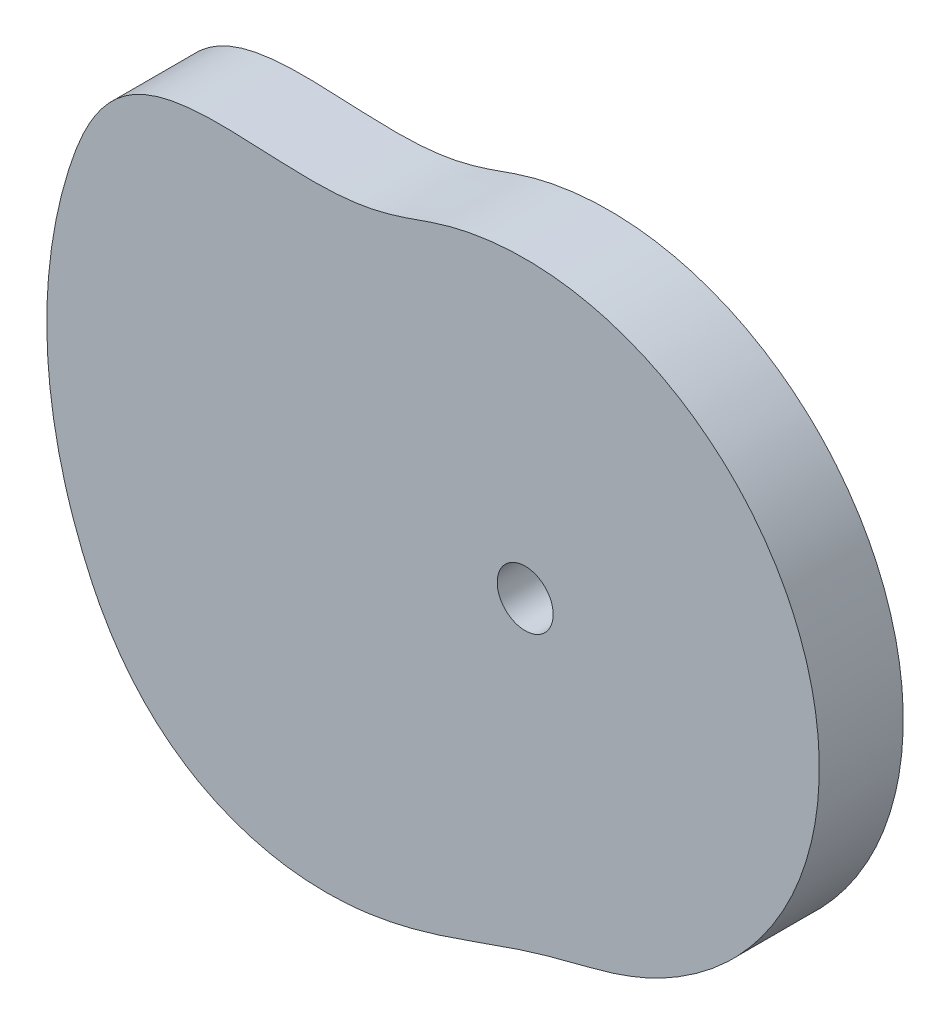
SolidWorks part; units mm, degrees
ref_plane "前视基准面" through (0, 0, 0) normal (0, 0, 1) x (1, 0, 0)
ref_plane "上视基准面" through (0, 0, 0) normal (0, 1, 0) x (1, 0, 0)
ref_plane "右视基准面" through (0, 0, 0) normal (1, 0, 0) x (0, 0, -1)
other "Configuration Table"
curve "曲线1"
sketch "草图1" plane through (0, 0, 0) normal (0, 0, 1) x (1, 0, 0)
  spline S0 degree 3 poles (71.0418, 77.4658) (70.3558, 78.0761) (69.666, 78.6826) (68.9824, 79.2894) (68.2921, 79.893) (67.5889, 80.4787) (66.8917, 81.0727) (66.1815, 81.6527) (65.4592, 82.219) (64.743, 82.7905) (64.018, 83.3518) (63.2913, 83.9128) (62.5525, 84.4601) (61.8092, 84.9989) (61.0716, 85.5435) (60.3217, 86.069) (59.5714, 86.5936) (58.8094, 87.0991) (58.0481, 87.6121) (57.2851, 88.1212) (56.508, 88.6121) (55.7293, 89.0988) (54.9554, 89.5922) (54.1673, 90.0611) (53.3826, 90.531) (52.5876, 90.9916) (51.7924, 91.4509) (50.9918, 91.8999) (50.1906, 92.3439) (49.379, 92.7682) (48.5708, 93.2047) (47.7488, 93.6177) (46.9352, 94.0438) (46.1089, 94.4378) (45.2904, 94.8444) (44.4569, 95.2305) (43.6268, 95.6209) (42.7874, 95.9918) (41.9493, 96.3584) (41.1122, 96.7362) (40.2591, 97.0779) (39.4121, 97.4317) (38.5618, 97.7714) (37.7068, 98.1003) (36.854, 98.4341) (35.9896, 98.7388) (35.127, 99.0509) (34.2637, 99.3642) (33.3894, 99.6483) (32.5216, 99.9416) (31.6489, 100.2237) (30.7694, 100.4879) (29.8934, 100.7648) (29.0097, 101.009) (28.1296, 101.2587) (27.2503, 101.5168) (26.3592, 101.7369) (25.473, 101.9754) (24.5796, 102.1786) (23.6868, 102.3905) (22.7956, 102.6036) (21.8965, 102.7894) (21.0012, 102.9823) (20.1008, 103.1609) (19.1979, 103.3335) (18.2929, 103.4876) (17.391, 103.6523) (16.4876, 103.8023) (15.5807, 103.9413) (14.6708, 104.0724) (13.7598, 104.1888) (12.8507, 104.3123) (11.9405, 104.4215) (11.0305, 104.5214) (10.1172, 104.613) (9.2032, 104.6882) (8.2905, 104.7725) (7.377, 104.8416) (6.4637, 104.9023) (5.5466, 104.9482) (4.6306, 105.006) (3.7132, 105.0277) (2.7968, 105.0626) (1.8801, 105.0824) (0.9633, 105.0878) (0.0467, 105.1062) (-0.87, 105.0875) (-1.7901, 105.0837) (-2.7066, 105.0576) (-3.6238, 105.0463) (-4.5398, 104.9965) (-5.4574, 104.9677) (-6.3728, 104.8937) (-7.2875, 104.8566) (-8.2004, 104.7812) (-9.1132, 104.6985) (-10.0272, 104.6229) (-10.9405, 104.5314) (-11.8505, 104.4315) (-12.7607, 104.3223) (-13.6698, 104.1988) (-14.5808, 104.0824) (-15.4906, 103.951) (-16.3978, 103.8135) (-17.3029, 103.6575) (-18.2078, 103.5135) (-19.1108, 103.3512) (-20.0109, 103.1814) (-20.9111, 103.0022) (-21.8065, 102.8095) (-22.7056, 102.6236) (-23.5968, 102.4105) (-24.4897, 102.1987) (-25.3829, 101.9952) (-26.2694, 101.7577) (-27.1586, 101.5341) (-28.044, 101.2889) (-28.9287, 101.0437) (-29.8068, 100.7806) (-30.6843, 100.5199) (-31.5587, 100.2531) (-32.4344, 99.9698) (-33.3168, 99.677) (-34.2166, 99.3829) (-35.1248, 99.0546) (-36.0548, 98.7408) (-36.9971, 98.4078) (-37.9526, 98.068) (-38.9301, 97.7269) (-39.9227, 97.3781) (-40.933, 97.029) (-41.9582, 96.6747) (-43.003, 96.329) (-44.0658, 95.9773) (-45.1441, 95.6254) (-46.2446, 95.2864) (-47.3643, 94.9549) (-48.5036, 94.6412) (-49.6527, 94.3117) (-50.827, 94.0213) (-52.0087, 93.7108) (-53.217, 93.4512) (-54.4338, 93.1732) (-55.6682, 92.9274) (-56.9187, 92.6963) (-58.1816, 92.4759) (-59.4617, 92.2755) (-60.7527, 92.0989) (-62.0519, 91.9255) (-63.3655, 91.776) (-64.6924, 91.6458) (-66.0297, 91.5387) (-67.3763, 91.4389) (-68.7324, 91.3425) (-70.1032, 91.2897) (-71.4798, 91.2378) (-72.8665, 91.1989) (-74.2598, 91.1654) (-75.6633, 91.1592) (-77.0734, 91.1578) (-78.4934, 91.1697) (-79.9203, 91.1836) (-81.3531, 91.236) (-82.7937, 91.2531) (-84.2399, 91.3124) (-85.6902, 91.3576) (-87.1469, 91.4177) (-88.6063, 91.4938) (-90.0736, 91.5466) (-91.5366, 91.6206) (-93.0033, 91.6902) (-94.4733, 91.7596) (-95.9431, 91.8322) (-97.4133, 91.8898) (-98.88, 91.9494) (-100.3464, 92.0127) (-101.81, 92.0589) (-103.2665, 92.1113) (-104.7164, 92.155) (-106.16, 92.1683) (-107.5966, 92.1918) (-109.0233, 92.2043) (-110.4401, 92.1911) (-111.8434, 92.1715) (-113.237, 92.1438) (-114.6172, 92.0941) (-115.9836, 92.0211) (-117.3341, 91.9447) (-118.6642, 91.844) (-119.9777, 91.7236) (-121.2746, 91.5845) (-122.5548, 91.4243) (-123.8119, 91.2457) (-125.0484, 91.0434) (-126.2625, 90.8263) (-127.4556, 90.584) (-128.6275, 90.3277) (-129.7763, 90.0344) (-130.9037, 89.7263) (-132.0088, 89.3974) (-133.0873, 89.0348) (-134.1478, 88.6553) (-135.1856, 88.2573) (-136.2028, 87.8343) (-137.201, 87.3864) (-138.1774, 86.9077) (-139.1314, 86.4021) (-140.0727, 85.8863) (-140.993, 85.3355) (-141.8907, 84.7544) (-142.7756, 84.1527) (-143.6454, 83.5217) (-144.5011, 82.8673) (-145.3394, 82.1779) (-146.1621, 81.4668) (-146.9698, 80.7169) (-147.7632, 79.9432) (-148.5493, 79.1387) (-149.3172, 78.3023) (-150.0628, 77.4285) (-150.811, 76.5408) (-151.5262, 75.6071) (-152.2369, 74.6474) (-152.9378, 73.6599) (-153.6169, 72.6366) (-154.2859, 71.5858) (-154.9501, 70.5118) (-155.5742, 69.3923) (-156.206, 68.2602) (-156.8177, 67.0973) (-157.4066, 65.9048) (-157.9835, 64.6865) (-158.5593, 63.4471) (-159.1004, 62.1783) (-159.6491, 60.8965) (-160.1635, 59.586) (-160.6737, 58.256) (-161.1775, 56.9084) (-161.6488, 55.5362) (-162.1375, 54.1581) (-162.5935, 52.7555) (-163.0408, 51.3413) (-163.4833, 49.9187) (-163.9098, 48.491) (-164.3366, 47.0604) (-164.7263, 45.619) (-165.1377, 44.1847) (-165.4989, 42.7363) (-165.8716, 41.2913) (-166.2339, 39.8425) (-166.5698, 38.3907) (-166.9056, 36.9394) (-167.2103, 35.4808) (-167.5131, 34.018) (-167.8002, 32.554) (-168.0821, 31.0877) (-168.354, 29.6219) (-168.6009, 28.1507) (-168.8421, 26.6775) (-169.0731, 25.2048) (-169.282, 23.7274) (-169.4809, 22.2506) (-169.6744, 20.7713) (-169.8407, 19.2904) (-170.0027, 17.8073) (-170.1501, 16.3237) (-170.2951, 14.8377) (-170.411, 13.3503) (-170.5211, 11.8603) (-170.6245, 10.3707) (-170.7008, 8.8802) (-170.7721, 7.3902) (-170.8308, 5.9002) (-170.8848, 4.4103) (-170.9099, 2.9201) (-170.9357, 1.4301) (-170.9275, -0.06) (-170.9345, -1.5534) (-170.9146, -3.0469) (-170.8675, -4.5399) (-170.8357, -6.0304) (-170.7699, -7.5201) (-170.7048, -9.0106) (-170.6107, -10.5003) (-170.5126, -11.9871) (-170.4003, -13.4736) (-170.2844, -14.961) (-170.1416, -16.4472) (-169.991, -17.9304) (-169.8344, -19.4113) (-169.6508, -20.8905) (-169.462, -22.3707) (-169.2607, -23.8505) (-169.0552, -25.3284) (-168.8209, -26.8007) (-168.581, -28.2707) (-168.3342, -29.7419) (-168.0606, -31.2107) (-167.783, -32.6779) (-167.4906, -34.1408) (-167.1939, -35.6022) (-166.8722, -37.0579) (-166.5407, -38.5109) (-166.204, -39.9626) (-165.8404, -41.4109) (-165.4733, -42.8584) (-165.0902, -44.3009) (-164.7044, -45.7431) (-164.2894, -47.1765) (-163.8832, -48.6129) (-163.4553, -50.0404) (-162.9976, -51.4592) (-162.5541, -52.8835) (-162.0824, -54.2986) (-161.6, -55.7111) (-161.1161, -57.1212) (-160.5973, -58.519) (-160.0942, -59.924) (-159.561, -61.3183) (-159.0261, -62.7117) (-158.4571, -64.0888) (-157.906, -65.4719) (-157.3199, -66.8414) (-156.7334, -68.2048) (-156.1417, -69.5637) (-155.5345, -70.9118) (-154.9024, -72.2445) (-154.2727, -73.5745) (-153.6211, -74.8889) (-152.9674, -76.2006) (-152.2784, -77.4909) (-151.595, -78.783) (-150.8808, -80.059) (-150.1674, -81.3315) (-149.4179, -82.5808) (-148.6771, -83.8318) (-147.8988, -85.0635) (-147.1165, -86.2919) (-146.3013, -87.4998) (-145.4825, -88.703) (-144.6433, -89.8963) (-143.7713, -91.0701) (-142.8946, -92.2393) (-142.0025, -93.3966) (-141.0808, -94.5327) (-140.1454, -95.6636) (-139.1772, -96.7734) (-138.208, -97.8832) (-137.2003, -98.9633) (-136.1808, -100.0339) (-135.1439, -101.0939) (-134.0801, -102.1337) (-133.0028, -103.1634) (-131.9029, -104.1778) (-130.7694, -105.1598) (-129.6328, -106.1486) (-128.4622, -107.1003) (-127.2813, -108.0478) (-126.0716, -108.9645) (-124.8386, -109.864) (-123.5955, -110.7526) (-122.3298, -111.618) (-121.0377, -112.4535) (-119.7351, -113.2836) (-118.4086, -114.088) (-117.0614, -114.8617) (-115.7027, -115.6272) (-114.3191, -116.3544) (-112.9197, -117.0662) (-111.5005, -117.7513) (-110.074, -118.4304) (-108.6178, -119.0493) (-107.1609, -119.6782) (-105.6823, -120.2645) (-104.1904, -120.8235) (-102.6874, -121.3647) (-101.1764, -121.886) (-99.6468, -122.3649) (-98.1094, -122.8226) (-96.5626, -123.2687) (-94.999, -123.6631) (-93.4319, -124.0413) (-91.8616, -124.4096) (-90.2813, -124.7202) (-88.6967, -125.0289) (-87.1043, -125.2893) (-85.51, -125.5499) (-83.911, -125.7516) (-82.3111, -125.9431) (-80.7115, -126.1151) (-79.1079, -126.256) (-77.5039, -126.3618) (-75.9008, -126.4553) (-74.3037, -126.5165) (-72.7067, -126.5382) (-71.1133, -126.5709) (-69.5233, -126.5383) (-67.9396, -126.5164) (-66.3625, -126.4561) (-64.7931, -126.3605) (-63.2293, -126.2634) (-61.6719, -126.1461) (-60.1222, -125.9941) (-58.583, -125.8202) (-57.051, -125.6481) (-55.5328, -125.43) (-54.0248, -125.2157) (-52.5283, -124.9734) (-51.0426, -124.711) (-49.5641, -124.4468) (-48.0995, -124.1492) (-46.6436, -123.8575) (-45.2067, -123.5297) (-43.7774, -123.2146) (-42.3653, -122.8722) (-40.9601, -122.526) (-39.5736, -122.1489) (-38.1941, -121.7861) (-36.8337, -121.3988) (-35.4795, -121.0266) (-34.1436, -120.6192) (-32.8111, -120.2241) (-31.4961, -119.8117) (-30.1911, -119.4038) (-28.9031, -118.9807) (-27.6227, -118.5618) (-26.3531, -118.1408) (-25.091, -117.7235) (-23.8457, -117.2928) (-22.6098, -116.8604) (-21.3849, -116.4289) (-20.1607, -116.0142) (-18.9528, -115.5814) (-17.7547, -115.1496) (-16.5626, -114.7322) (-15.3798, -114.3104) (-14.205, -113.8886) (-13.0301, -113.4857) (-11.8769, -113.0567) (-10.7197, -112.6609) (-9.5725, -112.2623) (-8.4321, -111.8573) (-7.2923, -111.4729) (-6.1645, -111.0801) (-5.0418, -110.6979) (-3.9223, -110.3331) (-2.812, -109.9573) (-1.6996, -109.6011) (-0.5944, -109.2399) (0.5055, -108.8896) (1.6006, -108.5518) (2.6834, -108.2059) (3.7725, -107.8948) (4.8434, -107.5558) (5.9206, -107.252) (6.9853, -106.9387) (8.0503, -106.6412) (9.1054, -106.3389) (10.1603, -106.0509) (11.2056, -105.7595) (12.2457, -105.4797) (13.2801, -105.2102) (14.307, -104.9413) (15.33, -104.6702) (16.3426, -104.4006) (17.3532, -104.1394) (18.3524, -103.8796) (19.3518, -103.6336) (20.3351, -103.3672) (21.3189, -103.1252) (22.2853, -102.8583) (23.2499, -102.6097) (24.2088, -102.3646) (25.155, -102.0973) (26.0989, -101.8548) (27.0266, -101.5896) (27.9519, -101.3333) (28.8619, -101.0586) (29.7738, -100.806) (30.6647, -100.5168) (31.5563, -100.2563) (32.4341, -99.969) (33.3041, -99.6823) (34.1766, -99.3928) (35.0346, -99.0775) (35.9039, -98.7843) (36.7616, -98.4608) (37.6195, -98.1287) (38.4798, -97.8047) (39.3289, -97.4573) (40.1823, -97.1269) (41.0214, -96.7554) (41.8697, -96.4038) (42.7098, -96.0335) (43.5417, -95.6464) (44.3798, -95.2736) (45.2099, -94.8834) (46.0291, -94.4781) (46.8551, -94.0835) (47.6694, -93.6587) (48.4875, -93.2417) (49.3049, -92.8225) (50.1071, -92.3809) (50.9127, -91.9416) (51.7092, -91.4886) (52.5107, -91.0438) (53.3018, -90.5798) (54.0925, -90.1108) (54.8774, -89.6313) (55.6613, -89.154) (56.4287, -88.658) (57.2061, -88.1728) (57.9643, -87.6597) (58.7359, -87.1621) (59.4876, -86.6413) (60.2426, -86.1203) (60.9925, -85.5901) (61.7379, -85.0517) (62.4817, -84.5135) (63.2092, -83.9589) (63.9426, -83.4101) (64.6713, -82.8526) (65.3922, -82.2794) (66.1087, -81.7025) (66.8186, -81.1224) (67.5226, -80.5398) (68.2222, -79.9492) (68.9217, -79.3524) (69.6091, -78.7427) (70.2885, -78.1284) (70.9765, -77.524) (71.6346, -76.8875) (72.3166, -76.2738) (72.9683, -75.6283) (73.6299, -74.9933) (74.2819, -74.3486) (74.9324, -73.7023) (75.5687, -73.042) (76.2032, -72.3797) (76.8285, -71.7086) (77.4629, -71.0454) (78.0719, -70.3583) (78.6797, -69.6698) (79.2893, -68.9823) (79.8931, -68.2921) (80.4787, -67.5889) (81.0727, -66.8917) (81.6527, -66.1815) (82.219, -65.4592) (82.7905, -64.743) (83.3518, -64.018) (83.9128, -63.2913) (84.4601, -62.5525) (84.9989, -61.8092) (85.5435, -61.0716) (86.069, -60.3217) (86.5936, -59.5714) (87.0991, -58.8094) (87.6121, -58.0481) (88.1212, -57.2851) (88.6121, -56.508) (89.0988, -55.7293) (89.5922, -54.9554) (90.0611, -54.1673) (90.531, -53.3826) (90.9916, -52.5876) (91.4509, -51.7924) (91.8999, -50.9918) (92.3439, -50.1906) (92.7682, -49.379) (93.2047, -48.5708) (93.6177, -47.7488) (94.0438, -46.9352) (94.4378, -46.1089) (94.8444, -45.2904) (95.2305, -44.4569) (95.6209, -43.6268) (95.9918, -42.7874) (96.3584, -41.9493) (96.7362, -41.1122) (97.0779, -40.2591) (97.4317, -39.4121) (97.7714, -38.5618) (98.1004, -37.7068) (98.4337, -36.8539) (98.7413, -35.9871) (99.0465, -35.1221) (99.3667, -34.2613) (99.6479, -33.3893) (99.9417, -32.5217) (100.2237, -31.6488) (100.4879, -30.7694) (100.7649, -29.8934) (101.0087, -29.0096) (101.2607, -28.1269) (101.5132, -27.246) (101.7389, -26.3564) (101.9751, -25.4729) (102.1787, -24.5797) (102.3905, -23.6868) (102.6036, -22.7956) (102.7894, -21.8965) (102.9823, -21.0012) (103.1609, -20.1008) (103.3335, -19.1979) (103.4876, -18.2929) (103.6523, -17.391) (103.8023, -16.4876) (103.9413, -15.5807) (104.0724, -14.6708) (104.1888, -13.7598) (104.3123, -12.8507) (104.4215, -11.9405) (104.5214, -11.0305) (104.613, -10.1172) (104.6882, -9.2032) (104.7725, -8.2905) (104.8416, -7.377) (104.9023, -6.4637) (104.9482, -5.5466) (105.006, -4.6306) (105.0277, -3.7132) (105.0626, -2.7968) (105.0824, -1.8801) (105.0878, -0.9633) (105.1062, -0.0467) (105.0875, 0.87) (105.0837, 1.7901) (105.0576, 2.7066) (105.0463, 3.6238) (104.9965, 4.5398) (104.9677, 5.4574) (104.8937, 6.3728) (104.8566, 7.2875) (104.7812, 8.2004) (104.6985, 9.1132) (104.6229, 10.0272) (104.5314, 10.9405) (104.4315, 11.8505) (104.3223, 12.7607) (104.1988, 13.6698) (104.0824, 14.5808) (103.951, 15.4906) (103.8135, 16.3978) (103.6575, 17.3029) (103.5135, 18.2078) (103.3512, 19.1108) (103.1814, 20.0109) (103.0022, 20.9111) (102.8095, 21.8065) (102.6236, 22.7056) (102.4105, 23.5968) (102.1987, 24.4897) (101.9952, 25.3829) (101.7577, 26.2694) (101.5341, 27.1586) (101.2889, 28.044) (101.0437, 28.9287) (100.7806, 29.8068) (100.5199, 30.6843) (100.2532, 31.5587) (99.9696, 32.4343) (99.6821, 33.304) (99.3929, 34.1767) (99.0775, 35.0346) (98.7843, 35.9039) (98.4608, 36.7616) (98.1287, 37.6195) (97.8047, 38.4798) (97.4573, 39.3289) (97.1269, 40.1823) (96.7554, 41.0214) (96.4038, 41.8697) (96.0335, 42.7098) (95.6464, 43.5417) (95.2736, 44.3798) (94.8834, 45.2099) (94.4781, 46.0291) (94.0835, 46.8551) (93.6587, 47.6694) (93.2417, 48.4875) (92.8225, 49.3049) (92.3809, 50.1071) (91.9416, 50.9127) (91.4886, 51.7092) (91.0438, 52.5107) (90.5798, 53.3018) (90.1108, 54.0925) (89.6313, 54.8774) (89.154, 55.6613) (88.658, 56.4287) (88.1728, 57.2061) (87.6597, 57.9643) (87.1621, 58.7359) (86.6413, 59.4876) (86.1203, 60.2426) (85.5901, 60.9925) (85.0517, 61.7379) (84.5135, 62.4817) (83.9589, 63.2092) (83.4101, 63.9426) (82.8526, 64.6713) (82.2794, 65.3922) (81.7025, 66.1087) (81.1224, 66.8186) (80.5398, 67.5226) (79.9492, 68.2222) (79.3524, 68.9217) (78.7427, 69.6091) (78.1284, 70.2885) (77.524, 70.9765) (76.8875, 71.6346) (76.2738, 72.3166) (75.6283, 72.9683) (74.9933, 73.6299) (74.3486, 74.2819) (73.7023, 74.9324) (73.042, 75.5687) (72.3797, 76.2032) (71.7087, 76.8286) (71.0418, 77.4658) (70.3558, 78.0761) (69.666, 78.6826) knots -0.003364 -0.002246 -0.001128 0 0.001103 0.002222 0.003334 0.004447 0.00556 0.006675 0.007792 0.008908 0.010017 0.011136 0.012257 0.013371 0.014485 0.015601 0.016711 0.017824 0.018937 0.02006 0.02117 0.02229 0.02341 0.024517 0.025634 0.026746 0.027868 0.028984 0.030094 0.031209 0.032324 0.033444 0.034565 0.035674 0.036783 0.037898 0.039024 0.040129 0.041245 0.042361 0.043479 0.044597 0.04571 0.046819 0.047939 0.04905 0.050162 0.051285 0.0524 0.053515 0.054626 0.055745 0.056864 0.057977 0.059089 0.060201 0.061319 0.062437 0.063549 0.06466 0.065784 0.066891 0.068009 0.069125 0.070239 0.071362 0.072474 0.073583 0.074702 0.07582 0.076936 0.078052 0.079167 0.08028 0.081392 0.082515 0.083625 0.084735 0.085856 0.086964 0.088084 0.089204 0.090311 0.09143 0.092548 0.093655 0.094773 0.095892 0.097011 0.098118 0.099237 0.100357 0.101466 0.102586 0.103696 0.104807 0.10593 0.107041 0.108154 0.109269 0.110385 0.111501 0.112619 0.113738 0.114848 0.115969 0.11708 0.118194 0.11931 0.120429 0.121535 0.122659 0.123771 0.124882 0.126 0.127118 0.128227 0.129351 0.130467 0.131571 0.13269 0.133801 0.134928 0.136081 0.137254 0.13845 0.139661 0.1409 0.142149 0.143438 0.144737 0.146048 0.147394 0.148751 0.150132 0.151532 0.152951 0.154391 0.155842 0.157311 0.158803 0.160299 0.161818 0.163356 0.16489 0.166457 0.168032 0.169616 0.17121 0.172813 0.174438 0.176073 0.177706 0.179364 0.181031 0.18271 0.184389 0.186091 0.187794 0.189508 0.191235 0.192973 0.194713 0.196464 0.198228 0.199992 0.201757 0.203546 0.205323 0.207112 0.20889 0.210679 0.21248 0.214257 0.216046 0.217835 0.219611 0.221387 0.223151 0.224902 0.226653 0.228392 0.230106 0.231821 0.233511 0.23519 0.236858 0.238503 0.240124 0.241724 0.243314 0.244882 0.24643 0.247945 0.249452 0.250928 0.252385 0.253828 0.255252 0.256649 0.258033 0.259402 0.260757 0.262087 0.26342 0.264747 0.266052 0.267358 0.268662 0.269963 0.271259 0.272565 0.273883 0.275187 0.276523 0.277848 0.279207 0.280565 0.281951 0.283348 0.284755 0.286185 0.287637 0.289111 0.290602 0.292116 0.293655 0.295207 0.29679 0.298384 0.299999 0.301641 0.303301 0.304984 0.306673 0.308387 0.310118 0.311869 0.313634 0.31541 0.317202 0.319013 0.320821 0.322637 0.324449 0.326266 0.328083 0.329891 0.33171 0.333527 0.335338 0.337146 0.338961 0.340773 0.342595 0.344402 0.34622 0.348033 0.349844 0.351665 0.35347 0.355286 0.3571 0.358912 0.360722 0.362543 0.36435 0.366168 0.367984 0.3698 0.371614 0.373428 0.375241 0.377054 0.378866 0.380678 0.382489 0.384301 0.386125 0.387937 0.38975 0.391563 0.393376 0.395191 0.397007 0.398812 0.400629 0.402449 0.404258 0.406068 0.40788 0.409695 0.411511 0.413328 0.415137 0.416948 0.418761 0.420578 0.422398 0.424208 0.42602 0.427837 0.429646 0.431456 0.433273 0.435093 0.436903 0.438717 0.440538 0.442347 0.444162 0.445973 0.447785 0.449603 0.451414 0.453229 0.455041 0.456853 0.458673 0.460486 0.462297 0.464107 0.465916 0.46773 0.469521 0.471323 0.473123 0.474901 0.47669 0.478474 0.480247 0.482026 0.483806 0.485581 0.487347 0.489119 0.490884 0.492661 0.494432 0.496199 0.49797 0.499752 0.501532 0.503301 0.505082 0.506869 0.508653 0.510454 0.512243 0.514041 0.515846 0.517652 0.519466 0.521282 0.523109 0.524937 0.526777 0.528611 0.530459 0.532313 0.534178 0.536033 0.537905 0.539791 0.541667 0.543563 0.545457 0.547356 0.549264 0.551184 0.553104 0.555026 0.556955 0.558892 0.560827 0.562766 0.564719 0.566657 0.568611 0.570571 0.572529 0.574493 0.576451 0.578411 0.580367 0.58234 0.584297 0.586259 0.588218 0.590174 0.592127 0.594089 0.596038 0.597985 0.599918 0.601864 0.603797 0.605719 0.607641 0.609553 0.611454 0.613356 0.61525 0.617133 0.619007 0.620872 0.622728 0.624563 0.626402 0.628231 0.630041 0.631853 0.633647 0.635417 0.637192 0.638947 0.640696 0.642433 0.64415 0.645855 0.647555 0.649244 0.650925 0.652582 0.654231 0.655869 0.657496 0.659111 0.660718 0.662302 0.663887 0.665455 0.667017 0.668567 0.670101 0.671624 0.673147 0.674654 0.676154 0.677635 0.679115 0.680584 0.682049 0.683503 0.684941 0.686375 0.687798 0.689216 0.690635 0.692039 0.693427 0.694815 0.696185 0.697558 0.698913 0.700267 0.701607 0.702946 0.70427 0.705595 0.706905 0.708199 0.709494 0.710777 0.71206 0.713316 0.714584 0.715826 0.71707 0.7183 0.719521 0.720727 0.721933 0.723131 0.724314 0.725488 0.72665 0.727816 0.728955 0.730101 0.731232 0.732343 0.73347 0.734573 0.735696 0.736804 0.737919 0.739039 0.740159 0.741272 0.742386 0.743497 0.744619 0.745735 0.746845 0.747966 0.749081 0.75019 0.7513 0.75242 0.75354 0.75465 0.75577 0.756881 0.757997 0.759113 0.760224 0.761342 0.762466 0.763579 0.764689 0.765799 0.766922 0.768028 0.769148 0.770257 0.771374 0.772498 0.773611 0.774723 0.775834 0.776953 0.778069 0.779193 0.780308 0.781413 0.782527 0.783648 0.784767 0.785878 0.786989 0.788107 0.789217 0.790335 0.791453 0.792562 0.793679 0.794797 0.795907 0.797025 0.798143 0.799254 0.800374 0.801493 0.802605 0.803718 0.804831 0.805946 0.807063 0.808179 0.809288 0.810407 0.811528 0.812642 0.813756 0.814872 0.815982 0.817095 0.818208 0.819331 0.820441 0.821561 0.822681 0.823788 0.824905 0.826017 0.827139 0.828255 0.829365 0.83048 0.831595 0.832716 0.833836 0.834945 0.836054 0.837169 0.838295 0.8394 0.840516 0.841632 0.84275 0.843868 0.844981 0.84609 0.84721 0.848321 0.849444 0.850556 0.851671 0.852786 0.853897 0.855016 0.856135 0.857248 0.85836 0.859484 0.86059 0.861708 0.86282 0.863931 0.865055 0.866162 0.86728 0.868396 0.86951 0.870633 0.871745 0.872854 0.873973 0.875091 0.876207 0.877323 0.878438 0.879551 0.880663 0.881786 0.882896 0.884006 0.885127 0.886235 0.887355 0.888475 0.889582 0.8907 0.891819 0.892926 0.894044 0.895163 0.896282 0.897389 0.898508 0.899628 0.900737 0.901857 0.902967 0.904078 0.9052 0.906312 0.907425 0.90854 0.909656 0.910772 0.91189 0.913009 0.914119 0.91524 0.916351 0.917465 0.918581 0.919699 0.920806 0.92193 0.923042 0.924153 0.925271 0.926389 0.927498 0.928622 0.929738 0.930842 0.931961 0.933072 0.934199 0.935302 0.936425 0.937533 0.938648 0.939768 0.940888 0.942001 0.943115 0.944226 0.945348 0.946464 0.947574 0.948695 0.94981 0.950919 0.952029 0.953149 0.954269 0.955379 0.956499 0.957609 0.958726 0.959842 0.960953 0.962071 0.963195 0.964308 0.965418 0.966528 0.967651 0.968757 0.969877 0.970986 0.972103 0.973227 0.97434 0.975452 0.976563 0.977682 0.978798 0.979922 0.981037 0.982142 0.983256 0.984377 0.985496 0.986607 0.987718 0.988836 0.989946 0.991064 0.992182 0.993291 0.994408 0.995526 0.996636 0.997754 0.998872 1 1.001103 1.002222 1.003334 only from (70.35, 78.08) to (70.35, 78.08) construction
  spline S1 degree 3 poles (71.0418, 77.4658) (70.3558, 78.0761) (69.666, 78.6826) (68.9824, 79.2894) (68.2921, 79.893) (67.5889, 80.4787) (66.8917, 81.0727) (66.1815, 81.6527) (65.4592, 82.219) (64.743, 82.7905) (64.018, 83.3518) (63.2913, 83.9128) (62.5525, 84.4601) (61.8092, 84.9989) (61.0716, 85.5435) (60.3217, 86.069) (59.5714, 86.5936) (58.8094, 87.0991) (58.0481, 87.6121) (57.2851, 88.1212) (56.508, 88.6121) (55.7293, 89.0988) (54.9554, 89.5922) (54.1673, 90.0611) (53.3826, 90.531) (52.5876, 90.9916) (51.7924, 91.4509) (50.9918, 91.8999) (50.1906, 92.3439) (49.379, 92.7682) (48.5708, 93.2047) (47.7488, 93.6177) (46.9352, 94.0438) (46.1089, 94.4378) (45.2904, 94.8444) (44.4569, 95.2305) (43.6268, 95.6209) (42.7874, 95.9918) (41.9493, 96.3584) (41.1122, 96.7362) (40.2591, 97.0779) (39.4121, 97.4317) (38.5618, 97.7714) (37.7068, 98.1003) (36.854, 98.4341) (35.9896, 98.7388) (35.127, 99.0509) (34.2637, 99.3642) (33.3894, 99.6483) (32.5216, 99.9416) (31.6489, 100.2237) (30.7694, 100.4879) (29.8934, 100.7648) (29.0097, 101.009) (28.1296, 101.2587) (27.2503, 101.5168) (26.3592, 101.7369) (25.473, 101.9754) (24.5796, 102.1786) (23.6868, 102.3905) (22.7956, 102.6036) (21.8965, 102.7894) (21.0012, 102.9823) (20.1008, 103.1609) (19.1979, 103.3335) (18.2929, 103.4876) (17.391, 103.6523) (16.4876, 103.8023) (15.5807, 103.9413) (14.6708, 104.0724) (13.7598, 104.1888) (12.8507, 104.3123) (11.9405, 104.4215) (11.0305, 104.5214) (10.1172, 104.613) (9.2032, 104.6882) (8.2905, 104.7725) (7.377, 104.8416) (6.4637, 104.9023) (5.5466, 104.9482) (4.6306, 105.006) (3.7132, 105.0277) (2.7968, 105.0626) (1.8801, 105.0824) (0.9633, 105.0878) (0.0467, 105.1062) (-0.87, 105.0875) (-1.7901, 105.0837) (-2.7066, 105.0576) (-3.6238, 105.0463) (-4.5398, 104.9965) (-5.4574, 104.9677) (-6.3728, 104.8937) (-7.2875, 104.8566) (-8.2004, 104.7812) (-9.1132, 104.6985) (-10.0272, 104.6229) (-10.9405, 104.5314) (-11.8505, 104.4315) (-12.7607, 104.3223) (-13.6698, 104.1988) (-14.5808, 104.0824) (-15.4906, 103.951) (-16.3978, 103.8135) (-17.3029, 103.6575) (-18.2078, 103.5135) (-19.1108, 103.3512) (-20.0109, 103.1814) (-20.9111, 103.0022) (-21.8065, 102.8095) (-22.7056, 102.6236) (-23.5968, 102.4105) (-24.4897, 102.1987) (-25.3829, 101.9952) (-26.2694, 101.7577) (-27.1586, 101.5341) (-28.044, 101.2889) (-28.9287, 101.0437) (-29.8068, 100.7806) (-30.6843, 100.5199) (-31.5587, 100.2531) (-32.4344, 99.9698) (-33.3168, 99.677) (-34.2166, 99.3829) (-35.1248, 99.0546) (-36.0548, 98.7408) (-36.9971, 98.4078) (-37.9526, 98.068) (-38.9301, 97.7269) (-39.9227, 97.3781) (-40.933, 97.029) (-41.9582, 96.6747) (-43.003, 96.329) (-44.0658, 95.9773) (-45.1441, 95.6254) (-46.2446, 95.2864) (-47.3643, 94.9549) (-48.5036, 94.6412) (-49.6527, 94.3117) (-50.827, 94.0213) (-52.0087, 93.7108) (-53.217, 93.4512) (-54.4338, 93.1732) (-55.6682, 92.9274) (-56.9187, 92.6963) (-58.1816, 92.4759) (-59.4617, 92.2755) (-60.7527, 92.0989) (-62.0519, 91.9255) (-63.3655, 91.776) (-64.6924, 91.6458) (-66.0297, 91.5387) (-67.3763, 91.4389) (-68.7324, 91.3425) (-70.1032, 91.2897) (-71.4798, 91.2378) (-72.8665, 91.1989) (-74.2598, 91.1654) (-75.6633, 91.1592) (-77.0734, 91.1578) (-78.4934, 91.1697) (-79.9203, 91.1836) (-81.3531, 91.236) (-82.7937, 91.2531) (-84.2399, 91.3124) (-85.6902, 91.3576) (-87.1469, 91.4177) (-88.6063, 91.4938) (-90.0736, 91.5466) (-91.5366, 91.6206) (-93.0033, 91.6902) (-94.4733, 91.7596) (-95.9431, 91.8322) (-97.4133, 91.8898) (-98.88, 91.9494) (-100.3464, 92.0127) (-101.81, 92.0589) (-103.2665, 92.1113) (-104.7164, 92.155) (-106.16, 92.1683) (-107.5966, 92.1918) (-109.0233, 92.2043) (-110.4401, 92.1911) (-111.8434, 92.1715) (-113.237, 92.1438) (-114.6172, 92.0941) (-115.9836, 92.0211) (-117.3341, 91.9447) (-118.6642, 91.844) (-119.9777, 91.7236) (-121.2746, 91.5845) (-122.5548, 91.4243) (-123.8119, 91.2457) (-125.0484, 91.0434) (-126.2625, 90.8263) (-127.4556, 90.584) (-128.6275, 90.3277) (-129.7763, 90.0344) (-130.9037, 89.7263) (-132.0088, 89.3974) (-133.0873, 89.0348) (-134.1478, 88.6553) (-135.1856, 88.2573) (-136.2028, 87.8343) (-137.201, 87.3864) (-138.1774, 86.9077) (-139.1314, 86.4021) (-140.0727, 85.8863) (-140.993, 85.3355) (-141.8907, 84.7544) (-142.7756, 84.1527) (-143.6454, 83.5217) (-144.5011, 82.8673) (-145.3394, 82.1779) (-146.1621, 81.4668) (-146.9698, 80.7169) (-147.7632, 79.9432) (-148.5493, 79.1387) (-149.3172, 78.3023) (-150.0628, 77.4285) (-150.811, 76.5408) (-151.5262, 75.6071) (-152.2369, 74.6474) (-152.9378, 73.6599) (-153.6169, 72.6366) (-154.2859, 71.5858) (-154.9501, 70.5118) (-155.5742, 69.3923) (-156.206, 68.2602) (-156.8177, 67.0973) (-157.4066, 65.9048) (-157.9835, 64.6865) (-158.5593, 63.4471) (-159.1004, 62.1783) (-159.6491, 60.8965) (-160.1635, 59.586) (-160.6737, 58.256) (-161.1775, 56.9084) (-161.6488, 55.5362) (-162.1375, 54.1581) (-162.5935, 52.7555) (-163.0408, 51.3413) (-163.4833, 49.9187) (-163.9098, 48.491) (-164.3366, 47.0604) (-164.7263, 45.619) (-165.1377, 44.1847) (-165.4989, 42.7363) (-165.8716, 41.2913) (-166.2339, 39.8425) (-166.5698, 38.3907) (-166.9056, 36.9394) (-167.2103, 35.4808) (-167.5131, 34.018) (-167.8002, 32.554) (-168.0821, 31.0877) (-168.354, 29.6219) (-168.6009, 28.1507) (-168.8421, 26.6775) (-169.0731, 25.2048) (-169.282, 23.7274) (-169.4809, 22.2506) (-169.6744, 20.7713) (-169.8407, 19.2904) (-170.0027, 17.8073) (-170.1501, 16.3237) (-170.2951, 14.8377) (-170.411, 13.3503) (-170.5211, 11.8603) (-170.6245, 10.3707) (-170.7008, 8.8802) (-170.7721, 7.3902) (-170.8308, 5.9002) (-170.8848, 4.4103) (-170.9099, 2.9201) (-170.9357, 1.4301) (-170.9275, -0.06) (-170.9345, -1.5534) (-170.9146, -3.0469) (-170.8675, -4.5399) (-170.8357, -6.0304) (-170.7699, -7.5201) (-170.7048, -9.0106) (-170.6107, -10.5003) (-170.5126, -11.9871) (-170.4003, -13.4736) (-170.2844, -14.961) (-170.1416, -16.4472) (-169.991, -17.9304) (-169.8344, -19.4113) (-169.6508, -20.8905) (-169.462, -22.3707) (-169.2607, -23.8505) (-169.0552, -25.3284) (-168.8209, -26.8007) (-168.581, -28.2707) (-168.3342, -29.7419) (-168.0606, -31.2107) (-167.783, -32.6779) (-167.4906, -34.1408) (-167.1939, -35.6022) (-166.8722, -37.0579) (-166.5407, -38.5109) (-166.204, -39.9626) (-165.8404, -41.4109) (-165.4733, -42.8584) (-165.0902, -44.3009) (-164.7044, -45.7431) (-164.2894, -47.1765) (-163.8832, -48.6129) (-163.4553, -50.0404) (-162.9976, -51.4592) (-162.5541, -52.8835) (-162.0824, -54.2986) (-161.6, -55.7111) (-161.1161, -57.1212) (-160.5973, -58.519) (-160.0942, -59.924) (-159.561, -61.3183) (-159.0261, -62.7117) (-158.4571, -64.0888) (-157.906, -65.4719) (-157.3199, -66.8414) (-156.7334, -68.2048) (-156.1417, -69.5637) (-155.5345, -70.9118) (-154.9024, -72.2445) (-154.2727, -73.5745) (-153.6211, -74.8889) (-152.9674, -76.2006) (-152.2784, -77.4909) (-151.595, -78.783) (-150.8808, -80.059) (-150.1674, -81.3315) (-149.4179, -82.5808) (-148.6771, -83.8318) (-147.8988, -85.0635) (-147.1165, -86.2919) (-146.3013, -87.4998) (-145.4825, -88.703) (-144.6433, -89.8963) (-143.7713, -91.0701) (-142.8946, -92.2393) (-142.0025, -93.3966) (-141.0808, -94.5327) (-140.1454, -95.6636) (-139.1772, -96.7734) (-138.208, -97.8832) (-137.2003, -98.9633) (-136.1808, -100.0339) (-135.1439, -101.0939) (-134.0801, -102.1337) (-133.0028, -103.1634) (-131.9029, -104.1778) (-130.7694, -105.1598) (-129.6328, -106.1486) (-128.4622, -107.1003) (-127.2813, -108.0478) (-126.0716, -108.9645) (-124.8386, -109.864) (-123.5955, -110.7526) (-122.3298, -111.618) (-121.0377, -112.4535) (-119.7351, -113.2836) (-118.4086, -114.088) (-117.0614, -114.8617) (-115.7027, -115.6272) (-114.3191, -116.3544) (-112.9197, -117.0662) (-111.5005, -117.7513) (-110.074, -118.4304) (-108.6178, -119.0493) (-107.1609, -119.6782) (-105.6823, -120.2645) (-104.1904, -120.8235) (-102.6874, -121.3647) (-101.1764, -121.886) (-99.6468, -122.3649) (-98.1094, -122.8226) (-96.5626, -123.2687) (-94.999, -123.6631) (-93.4319, -124.0413) (-91.8616, -124.4096) (-90.2813, -124.7202) (-88.6967, -125.0289) (-87.1043, -125.2893) (-85.51, -125.5499) (-83.911, -125.7516) (-82.3111, -125.9431) (-80.7115, -126.1151) (-79.1079, -126.256) (-77.5039, -126.3618) (-75.9008, -126.4553) (-74.3037, -126.5165) (-72.7067, -126.5382) (-71.1133, -126.5709) (-69.5233, -126.5383) (-67.9396, -126.5164) (-66.3625, -126.4561) (-64.7931, -126.3605) (-63.2293, -126.2634) (-61.6719, -126.1461) (-60.1222, -125.9941) (-58.583, -125.8202) (-57.051, -125.6481) (-55.5328, -125.43) (-54.0248, -125.2157) (-52.5283, -124.9734) (-51.0426, -124.711) (-49.5641, -124.4468) (-48.0995, -124.1492) (-46.6436, -123.8575) (-45.2067, -123.5297) (-43.7774, -123.2146) (-42.3653, -122.8722) (-40.9601, -122.526) (-39.5736, -122.1489) (-38.1941, -121.7861) (-36.8337, -121.3988) (-35.4795, -121.0266) (-34.1436, -120.6192) (-32.8111, -120.2241) (-31.4961, -119.8117) (-30.1911, -119.4038) (-28.9031, -118.9807) (-27.6227, -118.5618) (-26.3531, -118.1408) (-25.091, -117.7235) (-23.8457, -117.2928) (-22.6098, -116.8604) (-21.3849, -116.4289) (-20.1607, -116.0142) (-18.9528, -115.5814) (-17.7547, -115.1496) (-16.5626, -114.7322) (-15.3798, -114.3104) (-14.205, -113.8886) (-13.0301, -113.4857) (-11.8769, -113.0567) (-10.7197, -112.6609) (-9.5725, -112.2623) (-8.4321, -111.8573) (-7.2923, -111.4729) (-6.1645, -111.0801) (-5.0418, -110.6979) (-3.9223, -110.3331) (-2.812, -109.9573) (-1.6996, -109.6011) (-0.5944, -109.2399) (0.5055, -108.8896) (1.6006, -108.5518) (2.6834, -108.2059) (3.7725, -107.8948) (4.8434, -107.5558) (5.9206, -107.252) (6.9853, -106.9387) (8.0503, -106.6412) (9.1054, -106.3389) (10.1603, -106.0509) (11.2056, -105.7595) (12.2457, -105.4797) (13.2801, -105.2102) (14.307, -104.9413) (15.33, -104.6702) (16.3426, -104.4006) (17.3532, -104.1394) (18.3524, -103.8796) (19.3518, -103.6336) (20.3351, -103.3672) (21.3189, -103.1252) (22.2853, -102.8583) (23.2499, -102.6097) (24.2088, -102.3646) (25.155, -102.0973) (26.0989, -101.8548) (27.0266, -101.5896) (27.9519, -101.3333) (28.8619, -101.0586) (29.7738, -100.806) (30.6647, -100.5168) (31.5563, -100.2563) (32.4341, -99.969) (33.3041, -99.6823) (34.1766, -99.3928) (35.0346, -99.0775) (35.9039, -98.7843) (36.7616, -98.4608) (37.6195, -98.1287) (38.4798, -97.8047) (39.3289, -97.4573) (40.1823, -97.1269) (41.0214, -96.7554) (41.8697, -96.4038) (42.7098, -96.0335) (43.5417, -95.6464) (44.3798, -95.2736) (45.2099, -94.8834) (46.0291, -94.4781) (46.8551, -94.0835) (47.6694, -93.6587) (48.4875, -93.2417) (49.3049, -92.8225) (50.1071, -92.3809) (50.9127, -91.9416) (51.7092, -91.4886) (52.5107, -91.0438) (53.3018, -90.5798) (54.0925, -90.1108) (54.8774, -89.6313) (55.6613, -89.154) (56.4287, -88.658) (57.2061, -88.1728) (57.9643, -87.6597) (58.7359, -87.1621) (59.4876, -86.6413) (60.2426, -86.1203) (60.9925, -85.5901) (61.7379, -85.0517) (62.4817, -84.5135) (63.2092, -83.9589) (63.9426, -83.4101) (64.6713, -82.8526) (65.3922, -82.2794) (66.1087, -81.7025) (66.8186, -81.1224) (67.5226, -80.5398) (68.2222, -79.9492) (68.9217, -79.3524) (69.6091, -78.7427) (70.2885, -78.1284) (70.9765, -77.524) (71.6346, -76.8875) (72.3166, -76.2738) (72.9683, -75.6283) (73.6299, -74.9933) (74.2819, -74.3486) (74.9324, -73.7023) (75.5687, -73.042) (76.2032, -72.3797) (76.8285, -71.7086) (77.4629, -71.0454) (78.0719, -70.3583) (78.6797, -69.6698) (79.2893, -68.9823) (79.8931, -68.2921) (80.4787, -67.5889) (81.0727, -66.8917) (81.6527, -66.1815) (82.219, -65.4592) (82.7905, -64.743) (83.3518, -64.018) (83.9128, -63.2913) (84.4601, -62.5525) (84.9989, -61.8092) (85.5435, -61.0716) (86.069, -60.3217) (86.5936, -59.5714) (87.0991, -58.8094) (87.6121, -58.0481) (88.1212, -57.2851) (88.6121, -56.508) (89.0988, -55.7293) (89.5922, -54.9554) (90.0611, -54.1673) (90.531, -53.3826) (90.9916, -52.5876) (91.4509, -51.7924) (91.8999, -50.9918) (92.3439, -50.1906) (92.7682, -49.379) (93.2047, -48.5708) (93.6177, -47.7488) (94.0438, -46.9352) (94.4378, -46.1089) (94.8444, -45.2904) (95.2305, -44.4569) (95.6209, -43.6268) (95.9918, -42.7874) (96.3584, -41.9493) (96.7362, -41.1122) (97.0779, -40.2591) (97.4317, -39.4121) (97.7714, -38.5618) (98.1004, -37.7068) (98.4337, -36.8539) (98.7413, -35.9871) (99.0465, -35.1221) (99.3667, -34.2613) (99.6479, -33.3893) (99.9417, -32.5217) (100.2237, -31.6488) (100.4879, -30.7694) (100.7649, -29.8934) (101.0087, -29.0096) (101.2607, -28.1269) (101.5132, -27.246) (101.7389, -26.3564) (101.9751, -25.4729) (102.1787, -24.5797) (102.3905, -23.6868) (102.6036, -22.7956) (102.7894, -21.8965) (102.9823, -21.0012) (103.1609, -20.1008) (103.3335, -19.1979) (103.4876, -18.2929) (103.6523, -17.391) (103.8023, -16.4876) (103.9413, -15.5807) (104.0724, -14.6708) (104.1888, -13.7598) (104.3123, -12.8507) (104.4215, -11.9405) (104.5214, -11.0305) (104.613, -10.1172) (104.6882, -9.2032) (104.7725, -8.2905) (104.8416, -7.377) (104.9023, -6.4637) (104.9482, -5.5466) (105.006, -4.6306) (105.0277, -3.7132) (105.0626, -2.7968) (105.0824, -1.8801) (105.0878, -0.9633) (105.1062, -0.0467) (105.0875, 0.87) (105.0837, 1.7901) (105.0576, 2.7066) (105.0463, 3.6238) (104.9965, 4.5398) (104.9677, 5.4574) (104.8937, 6.3728) (104.8566, 7.2875) (104.7812, 8.2004) (104.6985, 9.1132) (104.6229, 10.0272) (104.5314, 10.9405) (104.4315, 11.8505) (104.3223, 12.7607) (104.1988, 13.6698) (104.0824, 14.5808) (103.951, 15.4906) (103.8135, 16.3978) (103.6575, 17.3029) (103.5135, 18.2078) (103.3512, 19.1108) (103.1814, 20.0109) (103.0022, 20.9111) (102.8095, 21.8065) (102.6236, 22.7056) (102.4105, 23.5968) (102.1987, 24.4897) (101.9952, 25.3829) (101.7577, 26.2694) (101.5341, 27.1586) (101.2889, 28.044) (101.0437, 28.9287) (100.7806, 29.8068) (100.5199, 30.6843) (100.2532, 31.5587) (99.9696, 32.4343) (99.6821, 33.304) (99.3929, 34.1767) (99.0775, 35.0346) (98.7843, 35.9039) (98.4608, 36.7616) (98.1287, 37.6195) (97.8047, 38.4798) (97.4573, 39.3289) (97.1269, 40.1823) (96.7554, 41.0214) (96.4038, 41.8697) (96.0335, 42.7098) (95.6464, 43.5417) (95.2736, 44.3798) (94.8834, 45.2099) (94.4781, 46.0291) (94.0835, 46.8551) (93.6587, 47.6694) (93.2417, 48.4875) (92.8225, 49.3049) (92.3809, 50.1071) (91.9416, 50.9127) (91.4886, 51.7092) (91.0438, 52.5107) (90.5798, 53.3018) (90.1108, 54.0925) (89.6313, 54.8774) (89.154, 55.6613) (88.658, 56.4287) (88.1728, 57.2061) (87.6597, 57.9643) (87.1621, 58.7359) (86.6413, 59.4876) (86.1203, 60.2426) (85.5901, 60.9925) (85.0517, 61.7379) (84.5135, 62.4817) (83.9589, 63.2092) (83.4101, 63.9426) (82.8526, 64.6713) (82.2794, 65.3922) (81.7025, 66.1087) (81.1224, 66.8186) (80.5398, 67.5226) (79.9492, 68.2222) (79.3524, 68.9217) (78.7427, 69.6091) (78.1284, 70.2885) (77.524, 70.9765) (76.8875, 71.6346) (76.2738, 72.3166) (75.6283, 72.9683) (74.9933, 73.6299) (74.3486, 74.2819) (73.7023, 74.9324) (73.042, 75.5687) (72.3797, 76.2032) (71.7087, 76.8286) (71.0418, 77.4658) (70.3558, 78.0761) (69.666, 78.6826) knots -0.003364 -0.002246 -0.001128 0 0.001103 0.002222 0.003334 0.004447 0.00556 0.006675 0.007792 0.008908 0.010017 0.011136 0.012257 0.013371 0.014485 0.015601 0.016711 0.017824 0.018937 0.02006 0.02117 0.02229 0.02341 0.024517 0.025634 0.026746 0.027868 0.028984 0.030094 0.031209 0.032324 0.033444 0.034565 0.035674 0.036783 0.037898 0.039024 0.040129 0.041245 0.042361 0.043479 0.044597 0.04571 0.046819 0.047939 0.04905 0.050162 0.051285 0.0524 0.053515 0.054626 0.055745 0.056864 0.057977 0.059089 0.060201 0.061319 0.062437 0.063549 0.06466 0.065784 0.066891 0.068009 0.069125 0.070239 0.071362 0.072474 0.073583 0.074702 0.07582 0.076936 0.078052 0.079167 0.08028 0.081392 0.082515 0.083625 0.084735 0.085856 0.086964 0.088084 0.089204 0.090311 0.09143 0.092548 0.093655 0.094773 0.095892 0.097011 0.098118 0.099237 0.100357 0.101466 0.102586 0.103696 0.104807 0.10593 0.107041 0.108154 0.109269 0.110385 0.111501 0.112619 0.113738 0.114848 0.115969 0.11708 0.118194 0.11931 0.120429 0.121535 0.122659 0.123771 0.124882 0.126 0.127118 0.128227 0.129351 0.130467 0.131571 0.13269 0.133801 0.134928 0.136081 0.137254 0.13845 0.139661 0.1409 0.142149 0.143438 0.144737 0.146048 0.147394 0.148751 0.150132 0.151532 0.152951 0.154391 0.155842 0.157311 0.158803 0.160299 0.161818 0.163356 0.16489 0.166457 0.168032 0.169616 0.17121 0.172813 0.174438 0.176073 0.177706 0.179364 0.181031 0.18271 0.184389 0.186091 0.187794 0.189508 0.191235 0.192973 0.194713 0.196464 0.198228 0.199992 0.201757 0.203546 0.205323 0.207112 0.20889 0.210679 0.21248 0.214257 0.216046 0.217835 0.219611 0.221387 0.223151 0.224902 0.226653 0.228392 0.230106 0.231821 0.233511 0.23519 0.236858 0.238503 0.240124 0.241724 0.243314 0.244882 0.24643 0.247945 0.249452 0.250928 0.252385 0.253828 0.255252 0.256649 0.258033 0.259402 0.260757 0.262087 0.26342 0.264747 0.266052 0.267358 0.268662 0.269963 0.271259 0.272565 0.273883 0.275187 0.276523 0.277848 0.279207 0.280565 0.281951 0.283348 0.284755 0.286185 0.287637 0.289111 0.290602 0.292116 0.293655 0.295207 0.29679 0.298384 0.299999 0.301641 0.303301 0.304984 0.306673 0.308387 0.310118 0.311869 0.313634 0.31541 0.317202 0.319013 0.320821 0.322637 0.324449 0.326266 0.328083 0.329891 0.33171 0.333527 0.335338 0.337146 0.338961 0.340773 0.342595 0.344402 0.34622 0.348033 0.349844 0.351665 0.35347 0.355286 0.3571 0.358912 0.360722 0.362543 0.36435 0.366168 0.367984 0.3698 0.371614 0.373428 0.375241 0.377054 0.378866 0.380678 0.382489 0.384301 0.386125 0.387937 0.38975 0.391563 0.393376 0.395191 0.397007 0.398812 0.400629 0.402449 0.404258 0.406068 0.40788 0.409695 0.411511 0.413328 0.415137 0.416948 0.418761 0.420578 0.422398 0.424208 0.42602 0.427837 0.429646 0.431456 0.433273 0.435093 0.436903 0.438717 0.440538 0.442347 0.444162 0.445973 0.447785 0.449603 0.451414 0.453229 0.455041 0.456853 0.458673 0.460486 0.462297 0.464107 0.465916 0.46773 0.469521 0.471323 0.473123 0.474901 0.47669 0.478474 0.480247 0.482026 0.483806 0.485581 0.487347 0.489119 0.490884 0.492661 0.494432 0.496199 0.49797 0.499752 0.501532 0.503301 0.505082 0.506869 0.508653 0.510454 0.512243 0.514041 0.515846 0.517652 0.519466 0.521282 0.523109 0.524937 0.526777 0.528611 0.530459 0.532313 0.534178 0.536033 0.537905 0.539791 0.541667 0.543563 0.545457 0.547356 0.549264 0.551184 0.553104 0.555026 0.556955 0.558892 0.560827 0.562766 0.564719 0.566657 0.568611 0.570571 0.572529 0.574493 0.576451 0.578411 0.580367 0.58234 0.584297 0.586259 0.588218 0.590174 0.592127 0.594089 0.596038 0.597985 0.599918 0.601864 0.603797 0.605719 0.607641 0.609553 0.611454 0.613356 0.61525 0.617133 0.619007 0.620872 0.622728 0.624563 0.626402 0.628231 0.630041 0.631853 0.633647 0.635417 0.637192 0.638947 0.640696 0.642433 0.64415 0.645855 0.647555 0.649244 0.650925 0.652582 0.654231 0.655869 0.657496 0.659111 0.660718 0.662302 0.663887 0.665455 0.667017 0.668567 0.670101 0.671624 0.673147 0.674654 0.676154 0.677635 0.679115 0.680584 0.682049 0.683503 0.684941 0.686375 0.687798 0.689216 0.690635 0.692039 0.693427 0.694815 0.696185 0.697558 0.698913 0.700267 0.701607 0.702946 0.70427 0.705595 0.706905 0.708199 0.709494 0.710777 0.71206 0.713316 0.714584 0.715826 0.71707 0.7183 0.719521 0.720727 0.721933 0.723131 0.724314 0.725488 0.72665 0.727816 0.728955 0.730101 0.731232 0.732343 0.73347 0.734573 0.735696 0.736804 0.737919 0.739039 0.740159 0.741272 0.742386 0.743497 0.744619 0.745735 0.746845 0.747966 0.749081 0.75019 0.7513 0.75242 0.75354 0.75465 0.75577 0.756881 0.757997 0.759113 0.760224 0.761342 0.762466 0.763579 0.764689 0.765799 0.766922 0.768028 0.769148 0.770257 0.771374 0.772498 0.773611 0.774723 0.775834 0.776953 0.778069 0.779193 0.780308 0.781413 0.782527 0.783648 0.784767 0.785878 0.786989 0.788107 0.789217 0.790335 0.791453 0.792562 0.793679 0.794797 0.795907 0.797025 0.798143 0.799254 0.800374 0.801493 0.802605 0.803718 0.804831 0.805946 0.807063 0.808179 0.809288 0.810407 0.811528 0.812642 0.813756 0.814872 0.815982 0.817095 0.818208 0.819331 0.820441 0.821561 0.822681 0.823788 0.824905 0.826017 0.827139 0.828255 0.829365 0.83048 0.831595 0.832716 0.833836 0.834945 0.836054 0.837169 0.838295 0.8394 0.840516 0.841632 0.84275 0.843868 0.844981 0.84609 0.84721 0.848321 0.849444 0.850556 0.851671 0.852786 0.853897 0.855016 0.856135 0.857248 0.85836 0.859484 0.86059 0.861708 0.86282 0.863931 0.865055 0.866162 0.86728 0.868396 0.86951 0.870633 0.871745 0.872854 0.873973 0.875091 0.876207 0.877323 0.878438 0.879551 0.880663 0.881786 0.882896 0.884006 0.885127 0.886235 0.887355 0.888475 0.889582 0.8907 0.891819 0.892926 0.894044 0.895163 0.896282 0.897389 0.898508 0.899628 0.900737 0.901857 0.902967 0.904078 0.9052 0.906312 0.907425 0.90854 0.909656 0.910772 0.91189 0.913009 0.914119 0.91524 0.916351 0.917465 0.918581 0.919699 0.920806 0.92193 0.923042 0.924153 0.925271 0.926389 0.927498 0.928622 0.929738 0.930842 0.931961 0.933072 0.934199 0.935302 0.936425 0.937533 0.938648 0.939768 0.940888 0.942001 0.943115 0.944226 0.945348 0.946464 0.947574 0.948695 0.94981 0.950919 0.952029 0.953149 0.954269 0.955379 0.956499 0.957609 0.958726 0.959842 0.960953 0.962071 0.963195 0.964308 0.965418 0.966528 0.967651 0.968757 0.969877 0.970986 0.972103 0.973227 0.97434 0.975452 0.976563 0.977682 0.978798 0.979922 0.981037 0.982142 0.983256 0.984377 0.985496 0.986607 0.987718 0.988836 0.989946 0.991064 0.992182 0.993291 0.994408 0.995526 0.996636 0.997754 0.998872 1 1.001103 1.002222 1.003334 only from (70.35, 78.08) to (70.35, 78.08)
extrude "凸台-拉伸1" add sketch "草图1" along normal blind 30
sketch "草图2" plane through (0, 0, 0) normal (0, 0, 1) x (1, 0, 0)
  circle A0 centre (0, 0) radius 10
extrude "切除-拉伸1" cut sketch "草图2" along normal blind 30
